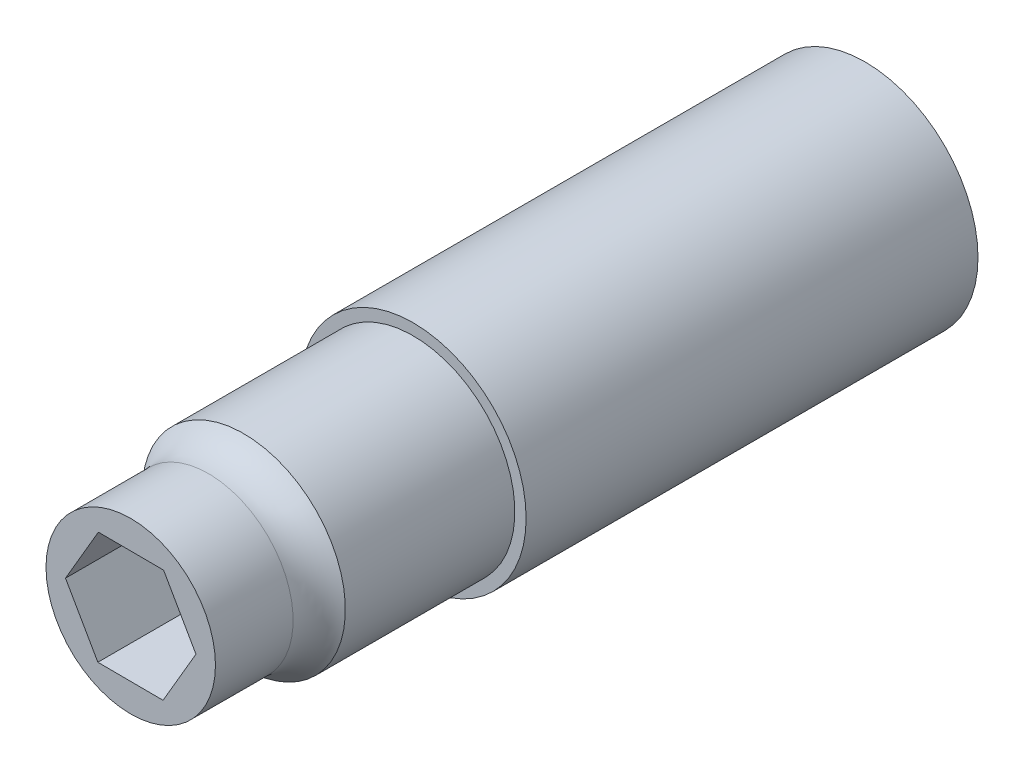
SolidWorks part; units mm, degrees
ref_plane "Front Plane" through (0, 0, 0) normal (0, 0, 1) x (1, 0, 0)
ref_plane "Top Plane" through (0, 0, 0) normal (0, 1, 0) x (1, 0, 0)
ref_plane "Right Plane" through (0, 0, 0) normal (1, 0, 0) x (0, 0, -1)
sketch "Sketch1" plane through (0, 0, 0) normal (0, 0, 1) x (1, 0, 0)
  circle A0 centre (0, 0) radius 12.7
extrude "Boss-Extrude1" add sketch "Sketch1" along normal blind 50.8
sketch "Sketch2" plane through (0, 0, 50.8) normal (0, 0, 1) x (1, 0, 0)
  circle A0 centre (0, 0) radius 11.43
  dimension "D1" = 22.86
extrude "Boss-Extrude2" add sketch "Sketch2" along normal blind 19.05
sketch "Sketch4" plane through (0, 0, 69.85) normal (0, 0, 1) x (1, 0, 0)
  circle A0 centre (0, 0) radius 9.525
extrude "Boss-Extrude3" add sketch "Sketch4" along normal blind 12.7
fillet "Fillet1" radius 5.08 1 edges at (9.525, 0, 69.85)
sketch "Sketch5" plane through (0, 0, 82.55) normal (0, 0, 1) x (1, 0, 0)
  line L1 (3.698, 6.3315) -> (-3.6342, 6.3683)
  line L2 (-3.6342, 6.3683) -> (-7.3323, 0.0369)
  line L3 (-7.3323, 0.0369) -> (-3.698, -6.3315)
  line L4 (-3.698, -6.3315) -> (3.6342, -6.3683)
  line L5 (3.6342, -6.3683) -> (7.3323, -0.0369)
  line L6 (7.3323, -0.0369) -> (3.698, 6.3315)
  circle A0 centre (0, 0) radius 6.35 construction
  dimension "D1" = 12.7
extrude "Cut-Extrude1" cut sketch "Sketch5" against normal blind 9.525
